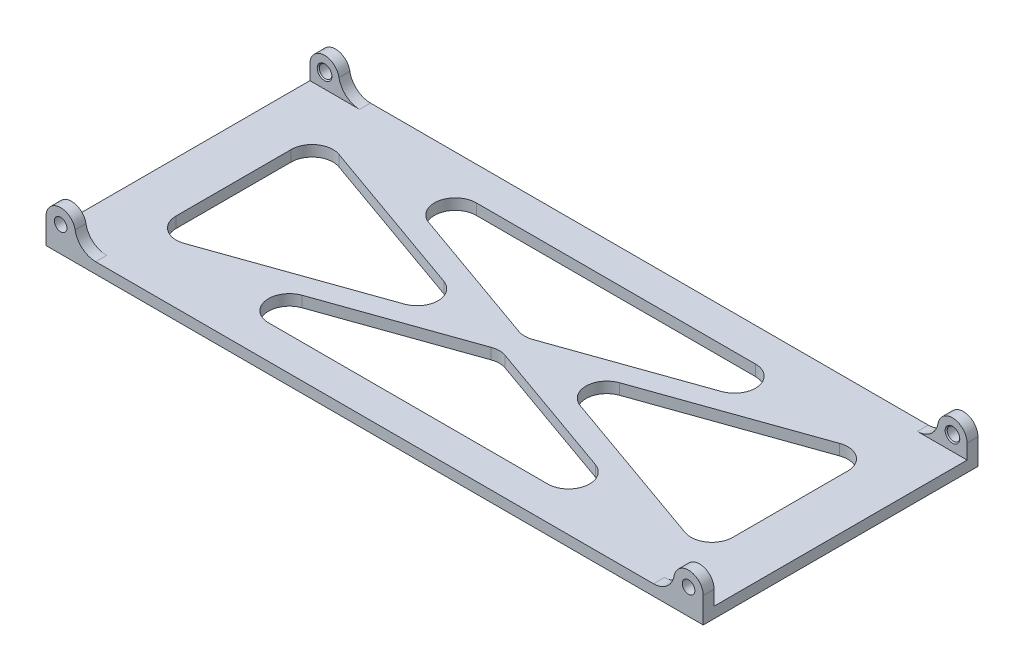
SolidWorks part; units mm, degrees
ref_plane "Front Plane" through (0, 0, 0) normal (0, 0, 1) x (1, 0, 0)
ref_plane "Top Plane" through (0, 0, 0) normal (0, 1, 0) x (1, 0, 0)
ref_plane "Right Plane" through (0, 0, 0) normal (1, 0, 0) x (0, 0, -1)
sketch "Sketch1" plane through (0, 0, 0) normal (0, 1, 0) x (1, 0, 0)
  line L1 (-78.45, -32.8) -> (78.45, -32.8)
  line L2 (-78.45, -32.8) -> (-78.45, 32.8)
  line L3 (-78.45, 32.8) -> (78.45, 32.8)
  line L4 (78.45, -32.8) -> (78.45, 32.8)
  line L5 (-78.45, -32.8) -> (78.45, 32.8) construction
  line L6 (-78.45, 32.8) -> (78.45, -32.8) construction
  point P0 (0, 0)
  dimension "D1" = 156.9
  dimension "D2" = 65.6
extrude "Boss-Extrude1" add sketch "Sketch1" along normal blind 2.6
sketch "Sketch2" plane through (0, 2.6, 0) normal (0, 1, 0) x (1, 0, 0)
  line L1 (-78.45, 32.8) -> (-71.45, 32.8)
  line L2 (-78.45, 32.8) -> (-78.45, 30.2)
  line L3 (-78.45, 30.2) -> (-71.45, 30.2)
  line L4 (-71.45, 32.8) -> (-71.45, 30.2)
  line L5 (-78.45, -32.8) -> (-71.45, -32.8)
  line L6 (-78.45, -32.8) -> (-78.45, -30.2)
  line L7 (-78.45, -30.2) -> (-71.45, -30.2)
  line L8 (-71.45, -32.8) -> (-71.45, -30.2)
  line L9 (78.45, -32.8) -> (71.45, -32.8)
  line L10 (78.45, -32.8) -> (78.45, -30.2)
  line L11 (78.45, -30.2) -> (71.45, -30.2)
  line L12 (71.45, -32.8) -> (71.45, -30.2)
  line L13 (78.45, 32.8) -> (71.45, 32.8)
  line L14 (78.45, 32.8) -> (78.45, 30.2)
  line L15 (78.45, 30.2) -> (71.45, 30.2)
  line L16 (71.45, 32.8) -> (71.45, 30.2)
  dimension "D1" = 2.6
  dimension "D2" = 2.6
  dimension "D3" = 7
extrude "Boss-Extrude2" add sketch "Sketch2" along normal blind 7
sketch "Sketch3" plane through (0, 0, -32.8) normal (0, 0, -1) x (-1, 0, 0)
  line L0 (-78.45, 9.6) -> (-78.45, 0) construction
  line L1 (-71.45, 9.6) -> (-71.45, 2.6) construction
  line L2 (-78.45, 6.1) -> (-78.45, 9.6)
  line L3 (-78.45, 9.6) -> (-71.45, 9.6)
  line L4 (-71.45, 9.6) -> (-71.45, 6.1)
  line L5 (0, 0) -> (0, 2.6) construction
  line L6 (-78.45, 0) -> (78.45, 0) construction
  line L7 (-71.45, 2.6) -> (71.45, 2.6) construction
  line L8 (71.45, 9.6) -> (71.45, 6.1)
  line L9 (78.45, 9.6) -> (71.45, 9.6)
  line L10 (78.45, 6.1) -> (78.45, 9.6)
  arc A0 (-78.45, 6.1) -> (-71.45, 6.1) centre (-74.95, 6.1) cw
  circle A1 centre (-74.95, 6.1) radius 1.5
  circle A2 centre (74.95, 6.1) radius 1.5
  arc A3 (78.45, 6.1) -> (71.45, 6.1) centre (74.95, 6.1) ccw
  line M4 (78.45, 0) -> (78.45, 9.6)
  line M5 (78.45, 9.6) -> (71.45, 9.6)
  line M6 (71.45, 9.6) -> (71.45, 2.6)
  line M8 (-71.45, 2.6) -> (-71.45, 9.6)
  line M9 (-71.45, 9.6) -> (-78.45, 9.6)
  line M10 (-78.45, 9.6) -> (-78.45, 0)
  dimension "D1" = 3.5
  dimension "D2" = 7
  dimension "D3" = 3
extrude "Cut-Extrude1" cut sketch "Sketch3" against normal through all contours A0 L3 M10 | A0 M9 M8 | A2 | A3 L9 M6 | A3 M4 M5 | A1 region at (72.2318, 8.8182, -32.8) region at (77.6682, 8.8182, -32.8) region at (-72.2318, 8.8182, -32.8) region at (-77.6682, 8.8182, -32.8) region at (-74.95, 6.1, -32.8)
fillet "Fillet1" radius 5 4 edges at (-71.45, 2.6, 31.5) (71.45, 2.6, 31.5) (71.45, 2.6, -31.5) (-71.45, 2.6, -31.5)
sketch "Sketch4" plane through (0, 2.6, 0) normal (0, 1, 0) x (1, 0, 0)
  line L8 (-62.45, -24.8) -> (0, -2.7075)
  line L9 (-78.45, -32.8) -> (-78.45, 32.8) construction
  line L10 (-78.45, -32.8) -> (78.45, -32.8) construction
  line L11 (78.45, -32.8) -> (78.45, 32.8) construction
  line L12 (-78.45, 32.8) -> (78.45, 32.8) construction
  line L13 (-66.45, -20.8) -> (-66.45, 20.8)
  line L14 (-62.45, -24.8) -> (62.45, -24.8)
  line L15 (66.45, -20.8) -> (66.45, 20.8)
  line L16 (-62.45, 24.8) -> (62.45, 24.8)
  line L17 (0, -2.7075) -> (62.45, -24.8)
  line L18 (-66.45, -20.8) -> (-7.6535, 0)
  line L19 (-7.6535, 0) -> (-66.45, 20.8)
  line L20 (-62.45, 24.8) -> (0, 2.7075)
  line L21 (0, 2.7075) -> (62.45, 24.8)
  line L22 (66.45, -20.8) -> (7.6535, 0)
  line L23 (7.6535, 0) -> (66.45, 20.8)
  line L24 (-66.45, -24.8) -> (-62.45, -24.8) construction
  line L25 (-66.45, -24.8) -> (-66.45, -20.8) construction
  line L26 (-66.45, 20.8) -> (-66.45, 24.8) construction
  line L27 (-66.45, 24.8) -> (-62.45, 24.8) construction
  line L28 (66.45, 20.8) -> (66.45, 24.8) construction
  line L29 (62.45, 24.8) -> (66.45, 24.8) construction
  line L30 (62.45, -24.8) -> (66.45, -24.8) construction
  line L31 (66.45, -24.8) -> (66.45, -20.8) construction
  line L32 (-78.45, 30.2) -> (-78.45, -30.2) construction
  line L33 (78.45, -30.2) -> (78.45, 30.2) construction
  line L34 (66.5834, 32.8) -> (-66.5834, 32.8) construction
  line L35 (-66.5834, -32.8) -> (66.5834, -32.8) construction
  dimension "D1" = 12
  dimension "D2" = 8
  dimension "D3" = 8
  dimension "D4" = 12
  dimension "D5" = 4
  dimension "D6" = 4
  dimension "D7" = 4
  dimension "D8" = 4
  dimension "D9" = 4
  dimension "D10" = 4
  dimension "D11" = 4
extrude "Cut-Extrude2" cut sketch "Sketch4" against normal blind 3.5
fillet "Fillet3" radius 5 12 edges at (-62.45, 1.3, 24.8) (-62.45, 1.3, -24.8) (66.45, 1.3, 20.8) (62.45, 1.3, 24.8) (66.45, 1.3, -20.8) (62.45, 1.3, -24.8) (7.6535, 1.3, 0) (0, 1.3, 2.7075) (0, 1.3, -2.7075) (-7.6535, 1.3, 0) (-66.45, 1.3, -20.8) (-66.45, 1.3, 20.8)
chamfer "Chamfer1" distance 0.25 angle 45 4 edges at (76.45, 6.1, 30.2) (73.45, 6.1, -30.2) (-76.45, 6.1, -30.2) (-73.45, 6.1, 30.2)
